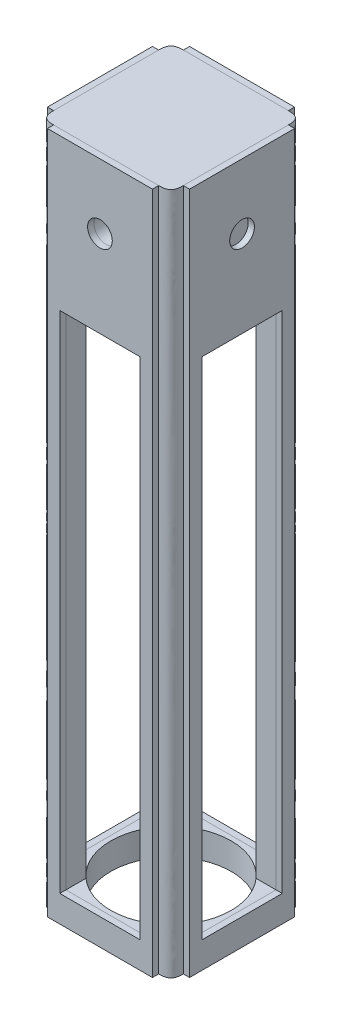
SolidWorks part; units mm, degrees
ref_plane "Front Plane" through (0, 0, 0) normal (0, 0, 1) x (1, 0, 0)
ref_plane "Top Plane" through (0, 0, 0) normal (0, 1, 0) x (1, 0, 0)
ref_plane "Right Plane" through (0, 0, 0) normal (1, 0, 0) x (0, 0, -1)
sketch "Sketch1" plane through (0, 0, 0) normal (1, 0, 0) x (0, 0, -1)
  line L0 (-28.3823, 0) -> (133.8141, 0) construction
  line L1 (44, 21) -> (86, 21)
  line L2 (44, 21) -> (44, -200)
  line L3 (44, -200) -> (86, -200)
  line L4 (86, 21) -> (86, -200)
  point P7 (65, 21)
  point P8 (133.8141, 0)
  dimension "D1" = 42
  dimension "D2" = 42
  dimension "D3" = 65
  dimension "D4" = 200
extrude "Boss-Extrude1" add sketch "Sketch1" along normal mid plane 42
sketch "Sketch2" plane through (0, 0, 0) normal (0, 0, 1) x (1, 0, 0)
  circle A0 centre (0, 0) radius 4
  dimension "D1" = 8
extrude "Cut-Extrude1" cut sketch "Sketch2" against normal through all
sketch "Sketch3" plane through (0, 0, 0) normal (0, 1, 0) x (1, 0, 0)
  circle A0 centre (0, 65) radius 19.5
  dimension "D1" = 39
  dimension "D2" = 65
extrude "Cut-Extrude2" cut sketch "Sketch3" against normal through all from offset 21 offset against normal yes
sketch "Sketch4" plane through (0, 0, 0) normal (1, 0, 0) x (0, 0, -1)
  line L0 (86, 21) -> (44, 21) construction
  line L1 (52, -28) -> (78, -28)
  line L2 (52, -28) -> (52, -191.4195)
  line L3 (52, -191.4195) -> (78, -191.4195)
  line L4 (78, -28) -> (78, -191.4195)
  point P4 (65, -28)
  point P7 (65, 21)
  dimension "D1" = 26
  dimension "D2" = 28
extrude "Cut-Extrude3" cut sketch "Sketch4" against normal through all both and the other way through all
pattern_circular "CirPattern1" count 2 over 90 about axis through (0, -200, -65) along (0, 1, 0) of "Cut-Extrude3"
fillet "Fillet1" radius 4 4 edges at (-21, -89.5, -86) (21, -89.5, -86) (-21, -89.5, -44) (21, -89.5, -44) curvature continuous yes
sketch "Sketch5" plane through (0, 0, -44) normal (0, 0, 1) x (1, 0, 0)
  line L0 (13, -191.4195) -> (-13, -191.4195) construction
  line L1 (13, -28) -> (13, -191.4195) construction
  line L2 (-13, -191.4195) -> (-13, -28) construction
  line L3 (-13, -28) -> (13, -28) construction
  line L4 (17, 21) -> (-17, 21)
  line L5 (-17, 21) -> (-17, -200)
  line L6 (-17, -200) -> (17, -200)
  line L7 (17, -200) -> (17, 21)
  line L8 (17, 21) -> (-17, 21)
  line L9 (-17, 21) -> (-17, -200)
  line L10 (-17, -200) -> (17, -200)
  line L11 (17, -200) -> (17, 21)
  line L12 (13, -191.4195) -> (-13, -191.4195)
  line L13 (13, -28) -> (13, -191.4195)
  line L14 (-13, -191.4195) -> (-13, -28)
  line L15 (-13, -28) -> (13, -28)
  circle A0 centre (0, 0) radius 4 construction
  circle A1 centre (0, 0) radius 4
  dimension "D1" = 0
extrude "Boss-Extrude2" add sketch "Sketch5" along normal blind 2 separate body
pattern_circular "CirPattern2" count 4 over 360 about axis through (0, -200, -65) along (0, 1, 0) of bodies 106
equation "\"spine_center_distance_to_axle\"= 65mm"
equation "\"spine_depth\"= 42mm"
equation "\"width\"= 42mm"
equation "\"D1@Sketch1\"=\"spine_depth\""
equation "\"D2@Sketch1\"=\"width\""
equation "\"D3@Sketch1\"=\"spine_center_distance_to_axle\""
equation "\"D1@Boss-Extrude1\"=\"width\""
equation "\"height\"= 200mm"
equation "\"D4@Sketch1\"=\"height\""
equation "\"D2@Sketch3\"=\"spine_center_distance_to_axle\""
equation "\"D19@Cut-Extrude2\"=\"width\"/2"
